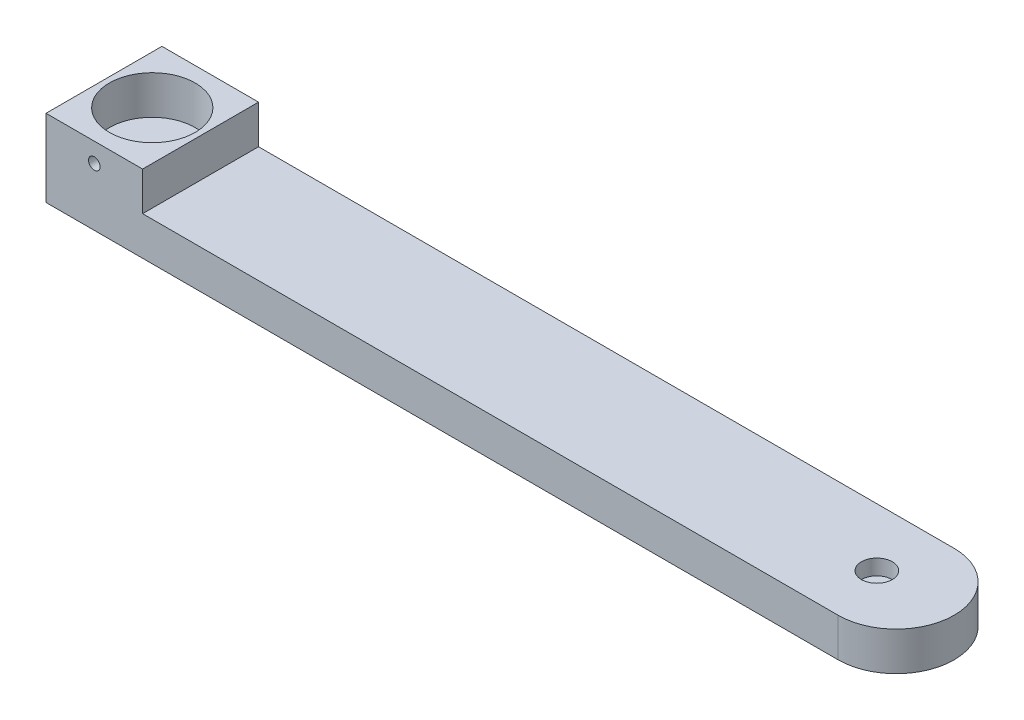
SolidWorks part; units mm, degrees
ref_plane "Front Plane" through (0, 0, 0) normal (0, 0, 1) x (1, 0, 0)
ref_plane "Top Plane" through (0, 0, 0) normal (0, 1, 0) x (1, 0, 0)
ref_plane "Right Plane" through (0, 0, 0) normal (1, 0, 0) x (0, 0, -1)
sketch "Sketch1" plane through (0, 0, 0) normal (0, 1, 0) x (1, 0, 0)
  line L1 (-110, -15) -> (110, -15)
  line L2 (-110, -15) -> (-110, 15)
  line L3 (-110, 15) -> (110, 15)
  line L4 (110, -15) -> (110, 15)
  line L5 (-110, -15) -> (110, 15) construction
  line L6 (-110, 15) -> (110, -15) construction
  circle A0 centre (95, 0) radius 15
  point P0 (0, 0)
  dimension "D3" = 30
  dimension "D1" = 220
  dimension "D2" = 30
extrude "Boss-Extrude1" add sketch "Sketch1" along normal blind 10 contours A0 L3 L2 L1 | A0 region at (-13.3615, 0, 0) region at (95, 0, 0)
sketch "Sketch2" plane through (0, 10, 0) normal (0, 1, 0) x (1, 0, 0)
  line L0 (-5.5, 0) -> (5.5, 0) construction
  line L2 (-85, -15) -> (-110, -15)
  line L3 (-85, -15) -> (-85, 15)
  line L4 (-85, 15) -> (-110, 15)
  line L5 (-110, -15) -> (-110, 15)
  line L6 (-85, -15) -> (-110, 15) construction
  line L7 (-85, 15) -> (-110, -15) construction
  circle A1 centre (-97.5, 0) radius 11.1
  dimension "D1" = 25
  dimension "D2" = 22.2
extrude "Boss-Extrude3" add sketch "Sketch2" along normal blind 10 contours L3 A1 region at (-97.5, 10, 14.6095)
sketch "Sketch4" plane through (0, 10, 0) normal (0, 1, 0) x (1, 0, 0)
  line L0 (-5.5, 0) -> (5.5, 0) construction
  circle A0 centre (90, 0) radius 4
  arc A1 (95, -15) -> (95, 15) centre (95, 0) ccw construction
  dimension "D1" = 8
  dimension "D2" = 5
sketch "Sketch6" plane through (0, 0, 15) normal (0, 0, 1) x (1, 0, 0)
  line L0 (-85, 10) -> (-110, 10) construction
  line L1 (-110, 20) -> (-110, 0) construction
  line L2 (-97.5, 20) -> (-97.5, 10) construction
  circle A0 centre (-97.5, 15) radius 1.5
  dimension "D1" = 3
extrude "Cut-Extrude2" cut sketch "Sketch6" against normal blind 10
extrude "Cut-Extrude3" cut sketch "Sketch4" against normal blind 4 from surface starting at face at (8.75, 10, 0)
sketch "Sketch7" plane through (0, 6, 0) normal (0, 1, 0) x (1, 0, 0)
  circle A0 centre (90, 0) radius 1.5
  dimension "D1" = 3
extrude "Cut-Extrude4" cut sketch "Sketch7" against normal blind 14
